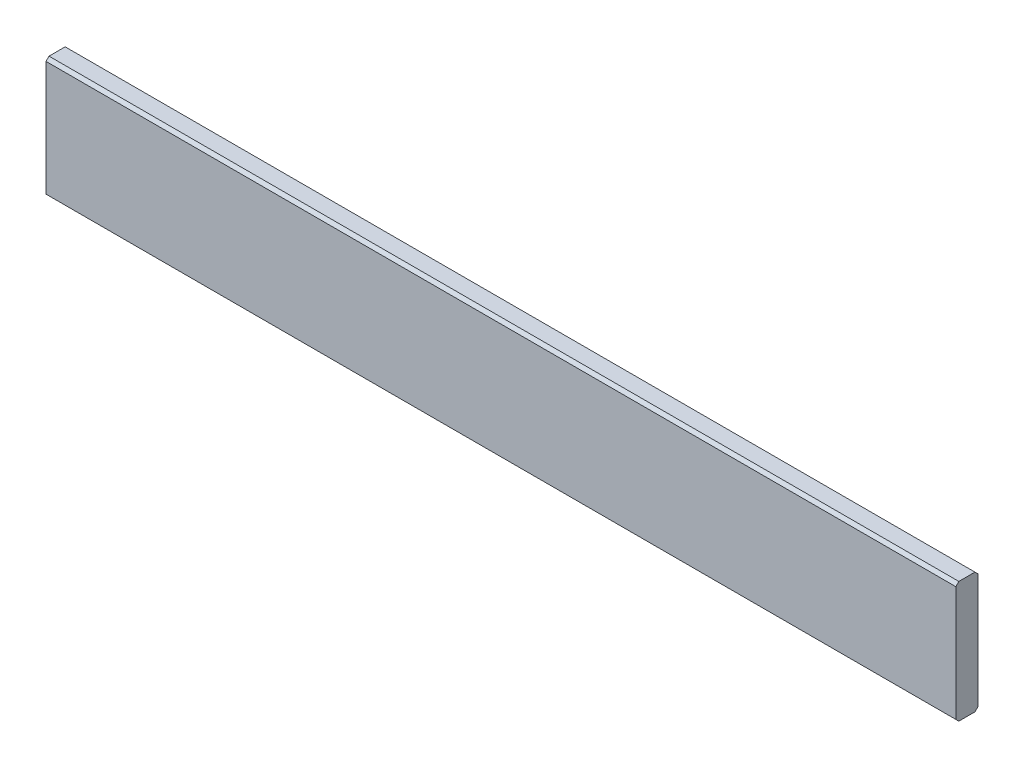
SolidWorks part; units mm, degrees
ref_plane "Plan de face" through (0, 0, 0) normal (0, 0, 1) x (1, 0, 0)
ref_plane "Plan de dessus" through (0, 0, 0) normal (0, 1, 0) x (1, 0, 0)
ref_plane "Plan de droite" through (0, 0, 0) normal (1, 0, 0) x (0, 0, -1)
sketch "Esquisse1" plane through (0, 0, 0) normal (0, 0, 1) x (1, 0, 0)
  line L1 (0, 0) -> (902, 0)
  line L2 (0, 0) -> (0, 120)
  line L3 (0, 120) -> (902, 120)
  line L4 (902, 0) -> (902, 120)
  dimension "D1" = 902
  dimension "D2" = 120
extrude "Boss.-Extru.1" add sketch "Esquisse1" along normal blind 22
chamfer "Chanfrein1" distance 3 angle 45 4 edges at (451, 0, 0) (451, 0, 22) (451, 120, 0) (451, 120, 22)
